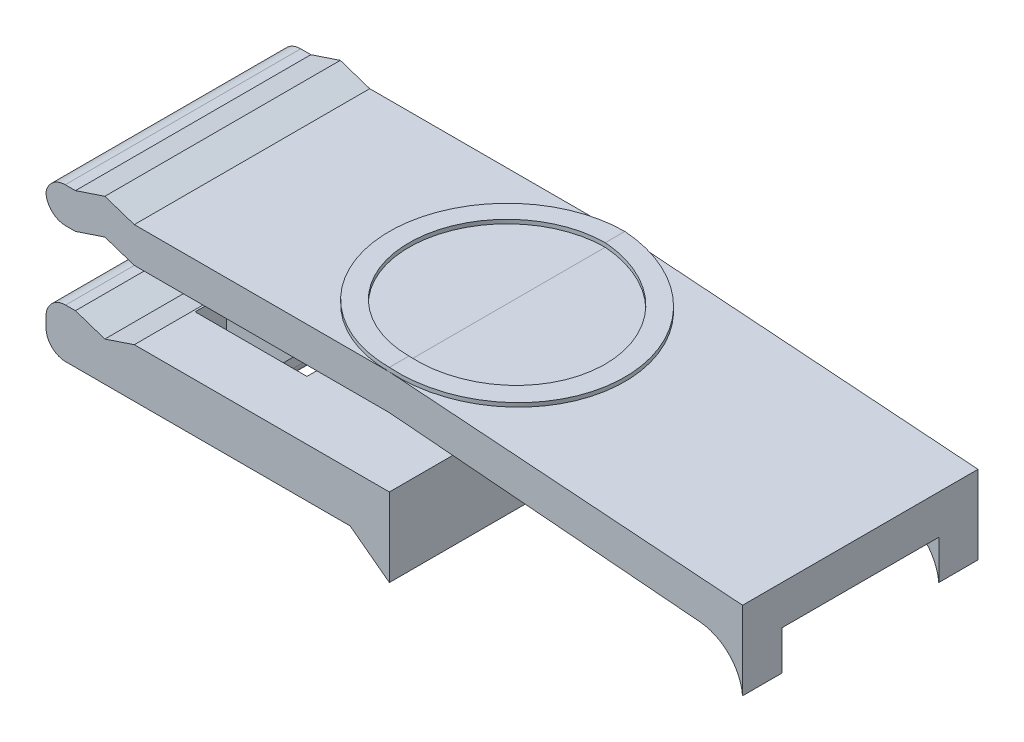
SolidWorks part; units mm, degrees
ref_plane "Front Plane" through (0, 0, 0) normal (0, 0, 1) x (1, 0, 0)
ref_plane "Top Plane" through (0, 0, 0) normal (0, 1, 0) x (1, 0, 0)
ref_plane "Right Plane" through (0, 0, 0) normal (1, 0, 0) x (0, 0, -1)
sketch "Sketch1" plane through (0, 0, 0) normal (0, 0, 1) x (1, 0, 0)
  line L0 (0, 0) -> (0, 4) construction
  line L1 (0, 0) -> (-18, 0) construction
  line L2 (0, 4) -> (-18, 5.3)
  line L3 (-18, 5.3) -> (-31, 5.3)
  line L4 (-31, 5.3) -> (-32.5, 5.8)
  line L5 (-32.5, 5.8) -> (-34, 5.3)
  line L6 (-34, 5.3) -> (-35.5, 5.3)
  line L7 (-35.5, 5.3) -> (-35.5, 3.5)
  line L8 (-35.5, -2.5) -> (-20, -2.5)
  line L9 (-20, -2.5) -> (-18, -4)
  line L10 (-35.5, 3.5) -> (-34, 3.5)
  line L11 (-34, 3.5) -> (-32.5, 4)
  line L12 (-18, 0) -> (-18, -4)
  line L13 (-18, 0) -> (-31, 0)
  line L14 (-31, 0) -> (-32.5, -0.5)
  line L15 (-32.5, -0.5) -> (-34, 0)
  line L16 (-34, 0) -> (-35.5, 0)
  line L17 (-35.5, 0) -> (-35.5, -2.5)
  line L18 (-32.5, 4) -> (-31, 3.5)
  line L19 (-31, 3.5) -> (-18, 3.5)
  line L20 (-18, 0) -> (-18, 5.3) construction
  line L21 (-18, 3.5) -> (0, 2)
  line L22 (0, 2) -> (0, 4)
  dimension "D1" = 13
  dimension "D2" = 18
  dimension "D3" = 0.5
  dimension "D4" = 2.5
  dimension "D5" = 1.5
  dimension "D6" = 3.5
  dimension "D7" = 1.5
  dimension "D8" = 2
  dimension "D9" = 0.5
  dimension "D10" = 2
  dimension "D11" = 0.5
  dimension "D12" = 1.8
  dimension "D13" = 1.5
  dimension "D15" = 3
  dimension "D16" = 1.5
extrude "Boss-Extrude1" add sketch "Sketch1" along normal blind 12
sketch "Sketch2" plane through (0, -2.5, 0) normal (0, -1, 0) x (1, 0, 0)
  line L0 (-20, 12) -> (-20, 0) construction
  line L1 (-30.9, 9) -> (-25.2, 9)
  line L2 (-30.9, 9) -> (-30.9, 3)
  line L3 (-30.9, 3) -> (-25.2, 3)
  line L4 (-25.2, 9) -> (-25.2, 3)
  line L5 (-31, 12) -> (-31, 0) construction
  line L7 (-20, 6) -> (-35.5, 6) construction
  line L8 (-35.5, 12) -> (-35.5, 0) construction
  point P9 (-25.2, 6)
  dimension "D1" = 0.1
  dimension "D2" = 5.7
  dimension "D3" = 6
extrude "Cut-Extrude1" cut sketch "Sketch2" against normal blind 3
sketch "Sketch3" plane through (0, 0, 3) normal (0, 0, 1) x (1, 0, 0)
  line L0 (-25.2, 0) -> (-27.2, -2)
  line L1 (-27.2, -2) -> (-27.2, -2.5)
  line L2 (-35.5, -2.5) -> (-20, -2.5) construction
  line L3 (-27.2, -2.5) -> (-25.2, -2.5)
  line L4 (-25.2, -2.5) -> (-25.2, 0)
  dimension "D1" = 0.5
  dimension "D2" = 2
extrude "Boss-Extrude2" add sketch "Sketch3" along normal up to surface (6 mm away) up to face at (-28.05, -1.25, 9)
sketch "Sketch4" plane through (0, 0, 12) normal (0, 0, 1) x (1, 0, 0)
  line L0 (-28.4, -2) -> (-26.4, 0)
  line L1 (-18, 0) -> (-31, 0) construction
  line L2 (-26.4, 0) -> (-26.4, 0.4)
  line L3 (-26.4, 0.4) -> (-27.9, 0.4)
  line L4 (-27.9, 0.4) -> (-27.9, 1.9)
  line L5 (-31, 3.5) -> (-18, 3.5) construction
  line L6 (-28.4, -2) -> (-28.4, -3)
  line L7 (-28.4, -3) -> (-29.8, -3)
  line L8 (-29.8, -3) -> (-29.8, 3.5)
  line L9 (-29.8, 3.5) -> (-26.3, 3.5)
  line L10 (-27.2, -2) -> (-27.2, -2.5) construction
  line L11 (-30.9, 0) -> (-30.9, -2.5) construction
  line L15 (-35.5, -2.5) -> (-20, -2.5) construction
  arc A1 (-27.9, 1.9) -> (-26.3, 3.5) centre (-26.3, 1.9) cw
  dimension "D1" = 1.5
  dimension "D2" = 1.2
  dimension "D3" = 45
  dimension "D4" = 0.4
  dimension "D5" = 1.4
  dimension "D6" = 1
  dimension "D7" = 2
  dimension "D8" = 1.5
  dimension "D9" = 1.1
  dimension "D11" = 0.8
  dimension "D13" = 2.9
  dimension "D14" = 3.1
extrude "Boss-Extrude3" add sketch "Sketch4" against normal mid plane 5 from offset 6 offset against normal yes
fillet "Fillet7" radius 1 1 edges at (-35.5, 0, 6)
fillet "Fillet8" radius 1 1 edges at (-35.5, 3.5, 6)
fillet "Fillet10" radius 1 1 edges at (-35.5, 5.3, 6)
fillet "Fillet11" radius 1 1 edges at (-35.5, -2.5, 6)
sketch "Sketch5" plane through (0, 0, 12) normal (0, 0, 1) x (1, 0, 0)
  line L0 (0, 2) -> (0, 0)
  line L1 (-18, 3.5) -> (0, 2) construction
  line L2 (-2.1818, 2.1818) -> (0, 2)
  arc A0 (-2.1818, 2.1818) -> (0, 0) centre (-2.3802, -0.1983) cw
extrude "Boss-Extrude4" add sketch "Sketch5" against normal blind 2
extrude "Boss-Extrude5" add sketch "Sketch5<2>" along normal blind 2 from offset 12 offset against normal yes
sketch "Sketch5<2>" plane through (0, 0, 12) normal (0, 0, 1) x (1, 0, 0) same geometry as "Sketch5"
fillet "Fillet12" radius 0.5 2 edges at (-28.4, -3, 6) (-29.8, -3, 6)
sketch "Sketch6" plane through (0, 0, 0) normal (0, 1, 0) x (1, 0, 0)
  line L1 (-18, -12) -> (-18, 0) construction
  circle A0 centre (-18, -6) radius 6
  circle A1 centre (-18, -6) radius 5
  dimension "D1" = 12
  dimension "D2" = 1
extrude "Boss-Extrude7" add sketch "Sketch6" against normal up to body from offset 5.5
sketch "Sketch7" plane through (0, 0, 0) normal (0, 0, 1) x (1, 0, 0)
  line L0 (-18, 5.5) -> (-12, 5.0667)
  line L1 (-12, 5.5) -> (-24, 5.5) construction
  line L2 (-12, 4.8667) -> (-12, 5.5) construction
  line L3 (-12, 5.0667) -> (-12, 5.5)
  line L4 (-12, 5.5) -> (-18, 5.5)
  line L5 (0, 4) -> (-18, 5.3) construction
extrude "Cut-Extrude3" cut sketch "Sketch7" along normal through all
